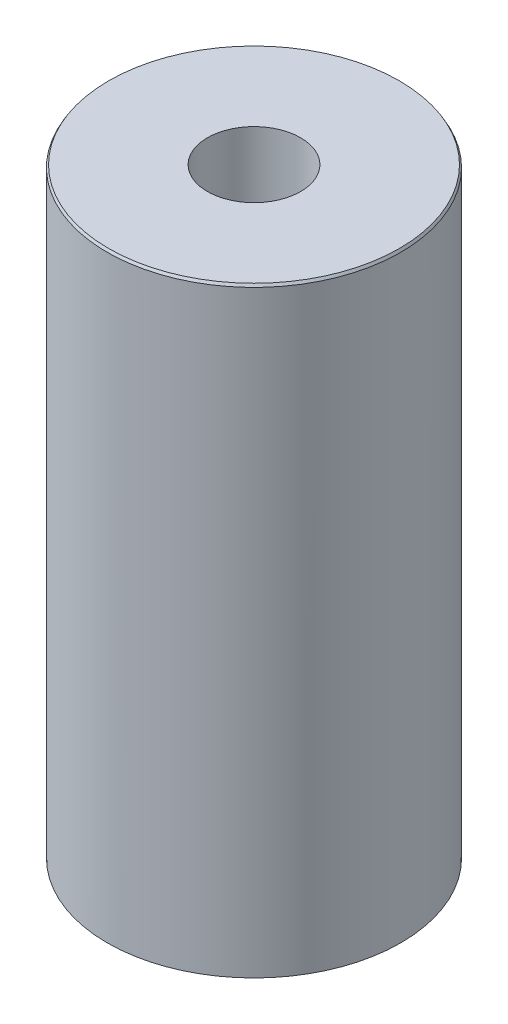
SolidWorks part; units mm, degrees
ref_plane "Front Plane" through (0, 0, 0) normal (0, 0, 1) x (1, 0, 0)
ref_plane "Top Plane" through (0, 0, 0) normal (0, 1, 0) x (1, 0, 0)
ref_plane "Right Plane" through (0, 0, 0) normal (1, 0, 0) x (0, 0, -1)
sketch "Sketch1" plane through (0, 0, 0) normal (0, 1, 0) x (1, 0, 0)
  circle A0 centre (0, 0) radius 57.5
  dimension "SHAFT_OD" = 115
extrude "Boss-Extrude1" add sketch "Sketch1" along normal blind 235.8731
sketch "Sketch2" plane through (0, 0, 0) normal (0, 1, 0) x (1, 0, 0)
  circle A0 centre (0, 0) radius 18.2655
  dimension "BORE_D" = 36.5311
extrude "Cut-Extrude1" cut sketch "Sketch2" along normal through all
chamfer "Chamfer1" distance 0.9975 angle 30 2 edges at (0, 235.8731, 57.5) (0, 0, 57.5) first distance on face at (0, 235.8731, 57.5) first distance on face at (0, 0, 18.2655)
